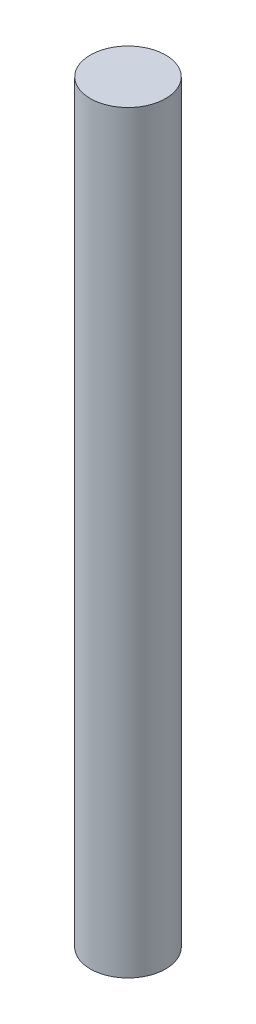
SolidWorks part; units mm, degrees
ref_plane "Front Plane" through (0, 0, 0) normal (0, 0, 1) x (1, 0, 0)
ref_plane "Top Plane" through (0, 0, 0) normal (0, 1, 0) x (1, 0, 0)
ref_plane "Right Plane" through (0, 0, 0) normal (1, 0, 0) x (0, 0, -1)
sketch "Sketch1" plane through (0, 0, 0) normal (0, 1, 0) x (1, 0, 0)
  circle A0 centre (0, 0) radius 2.5
  dimension "D1" = 5
extrude "Boss-Extrude1" add sketch "Sketch1" along normal blind 50
sketch "Sketch2" plane through (0, 0, 0) normal (0, -1, 0) x (-1, 0, 0)
  line L0 (1.5, 0) -> (-1.5, 0)
  circle A0 centre (0, 0) radius 1.5
  dimension "D1" = 3
extrude "Cut-Extrude1" cut sketch "Sketch2" against normal blind 9 contours L0 A0 | A0 region at (0, 0, 0.6366)
ref_axis "Axis1" through (0, 50, 0) along (0, -1, 0)
